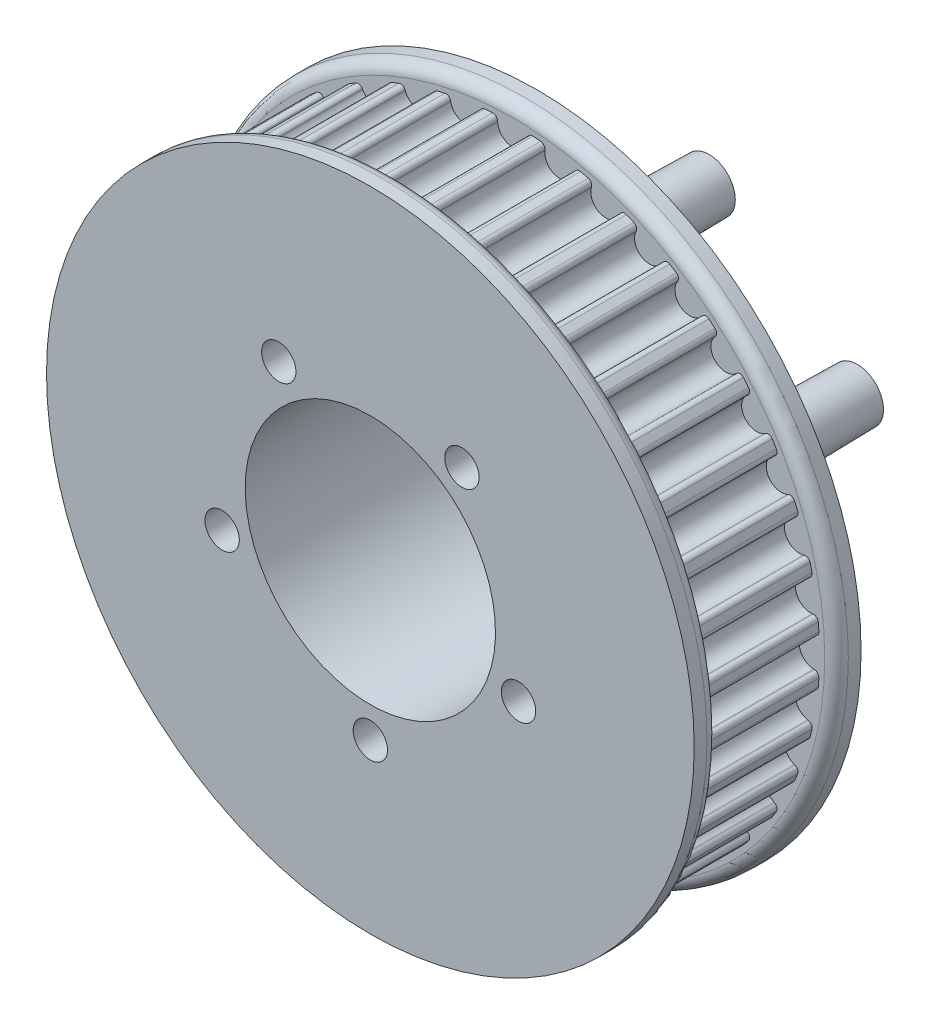
SolidWorks part; units mm, degrees
ref_plane "정면" through (0, 0, 0) normal (0, 0, 1) x (1, 0, 0)
ref_plane "윗면" through (0, 0, 0) normal (0, 1, 0) x (1, 0, 0)
ref_plane "우측면" through (0, 0, 0) normal (1, 0, 0) x (0, 0, -1)
sketch "스케치3" plane through (0, 0, 0) normal (0, 0, 1) x (1, 0, 0)
  line L0 (0, 0) -> (0, 31.2595) construction
  line L1 (0, 0) -> (-4.9795, 31.4391) construction
  line L2 (0, 31.2595) -> (0, 32.9895) construction
  line L3 (-1.5331, 30.6478) -> (-1.5617, 31.2205)
  line L4 (1.5331, 30.6478) -> (1.5617, 31.2205)
  circle A0 centre (0, 0) radius 31.831 construction
  circle A1 centre (0, 0) radius 32.9895 construction
  circle A2 centre (0, 0) radius 31.2595
  circle A3 centre (0, 30.7245) radius 1.535
  dimension "D2" = 63.662
  dimension "D5" = 3.07
  dimension "D3" = 62.519
  dimension "D1" = 9
  dimension "D4" = 2.07
  dimension "D6" = 3.8
extrude "보스-돌출2" add sketch "스케치3" along normal blind 12 contours A2
extrude "컷-돌출2" cut sketch "스케치3<3>" against normal through all and the other way through all contours A3 A2 L3 | A2 A3 | A3 L4 A2 region at (0, 30.3451, 0) region at (-1.5216, 31.0799, 0) region at (1.5216, 31.0799, 0)
sketch "스케치3<3>" plane through (0, 0, 0) normal (0, 0, 1) x (1, 0, 0) same geometry as "스케치3"
fillet "필렛1" radius 0.48 2 edges at (1.5617, 31.2205, 6) (-1.5617, 31.2205, 6)
pattern_circular "원형 패턴1" count 40 over 360 about axis through (0, 0, 12) along (0, 0, -1) of "컷-돌출2", "필렛1"
sketch "스케치8" plane through (0, 0, 12) normal (0, 0, 1) x (1, 0, 0)
  circle A1 centre (0, 0) radius 32.9895 construction
  circle A2 centre (0, 0) radius 32.9895
extrude "보스-돌출3" add sketch "스케치8" along normal blind 2.5
sketch "스케치9" plane through (0, 0, 0) normal (0, 0, -1) x (-1, 0, 0)
  circle A1 centre (0, 0) radius 32.9895 construction
  circle A3 centre (0, 0) radius 32.9895
extrude "보스-돌출4" add sketch "스케치9" along normal blind 2.5
sketch "스케치7" plane through (0, 0, 0) normal (-1, 0, 0) x (0, 0, 1)
  line L0 (-14.6599, 0) -> (-14.6599, 11)
  line L1 (-14.6599, 0) -> (-1.0048, 0)
  line L3 (-2.5, 32.9895) -> (-2.5, -32.9895) construction
  line L5 (-7.2548, 22.06) -> (-7.2548, 0) construction
  line L6 (-1.0048, 0) -> (-1.0048, 34.5)
  line L7 (0.2952, 26.3473) -> (-4.9, 29.3467)
  line L9 (-7.2548, 22.06) -> (0.2952, 22.06)
  line L10 (-7.2548, 22.06) -> (-10.1591, 0) construction
  line L13 (0.2952, 26.3473) -> (0.2952, 22.06)
  arc A0 (-14.6599, 11) -> (-7.2548, 22.06) centre (-2.698, 11) cw
  arc A1 (-7.2548, 22.06) -> (-1.0048, 34.5) centre (13.7562, 19.2938) cw
  dimension "D1" = 11
  dimension "D2" = 2.4
  dimension "D3" = 6.25
  dimension "D4" = 34.5
  dimension "D5" = 22.06
  dimension "D6" = 7.5
  dimension "D7" = 30
  dimension "D8" = 13.6551
  dimension "D10" = 7.55
  dimension "D11" = 3.8952
revolve "회전2" add sketch "스케치7" angle 360 about L1 region at (0, 10.341, -7.4409) region at (0, 25.0336, -3.8864)
sketch "스케치10" plane through (0, 0, 0) normal (0, 0, 1) x (1, 0, 0)
  line L0 (0, 0) -> (0, 15.875) construction
  circle A0 centre (0, 15.875) radius 2.675
  circle A1 centre (9.3311, 12.8431) radius 2.675 construction
  circle A2 centre (15.098, 4.9056) radius 2.675
  circle A3 centre (15.098, -4.9056) radius 2.675 construction
  circle A4 centre (9.3311, -12.8431) radius 2.675
  circle A5 centre (0, -15.875) radius 2.675 construction
  circle A6 centre (-9.3311, -12.8431) radius 2.675
  circle A7 centre (-15.098, -4.9056) radius 2.675 construction
  circle A8 centre (-15.098, 4.9056) radius 2.675
  circle A9 centre (-9.3311, 12.8431) radius 2.675 construction
  point P25 (0, 0)
  dimension "D1" = 5.35
  dimension "D2" = 15.875
  dimension "D3" = 10
extrude "보스-돌출5" add sketch "스케치10" against normal blind 20
hole_wizard "M5x0.8 탭을 위한 탭 드릴2" positions "스케치14" profile "스케치15" hole size "M5x0.8" standard "Ansi Metric" end condition through all
sketch "스케치14" plane through (0, 0, 14.5) normal (0, 0, -1) x (-1, 0, 0)
  point P26 (-15.098, -4.9056)
  point P28 (0, -15.875)
  point P30 (15.098, -4.9056)
  point P32 (9.3311, 12.8431)
  point P34 (-9.3311, 12.8431)
sketch "스케치15" plane through (15.098, -4.9056, 14.5) normal (1, 0, 0) x (0, -1, 0)
  line L0 (0, 0) -> (0, 34.5)
  line L1 (0, 34.5) -> (1.75, 34.5)
  line L2 (1.75, 34.5) -> (1.75, 0)
  line L5 (1.75, 0) -> (0, 0)
  line L11 (0, -6.35) -> (0, 107.95) construction
  dimension "관통 구멍 지름" = 3.5
  dimension "관통 구멍 깊이" = 34.5
draft "구배1" type of draft neutral plane draft angle 1 faces to draft 5 face at (17.2692, 6.4682, -12.064) face at (11.6645, -11.5352, -13.3692) face at (-6.94, -11.6438, -14.3838) face at (-13.0972, 6.6812, -14.0724) face at (1.7472, 17.9006, -12.4082) neutral plane through (0, 15.875, -20) neutral plane normal (0, 0, -1) parameters "D1"=1
sketch "스케치4" plane through (0, 0, -14.6599) normal (0, 0, -1) x (-1, 0, 0)
  circle A1 centre (0, 0) radius 12.75
  dimension "D1" = 25.5
extrude "컷-돌출3" cut sketch "스케치4" against normal through all
fillet "필렛2" radius 1.2 2 edges at (32.9895, 0, 12) (-32.9895, 0, 0)
sketch "스케치16" plane through (0, 0, -2.5) normal (0, 0, 1) x (1, 0, 0)
  circle A0 centre (0, 0) radius 22.5
  dimension "D1" = 45
extrude "컷-돌출4" [suppressed] cut sketch "스케치16" along normal through all from offset 10
sketch "스케치17" plane through (0, 0, 0) normal (1, 0, 0) x (0, 0, -1)
  line L0 (0, 0) -> (-50000, 0) construction
  line L2 (2.5, 32.9895) -> (2.5, 20)
  line L3 (2.5, -27.9611) -> (2.5, 27.9611) construction
  line L4 (2.5, 20) -> (8.2548, 20)
  line L5 (8.2548, 20) -> (8.2548, 0)
  line L7 (7.2548, 22.06) -> (7.2548, -22.06) construction
  dimension "D1" = 1
  dimension "D2" = 40
surface "곡면-회전1" [suppressed] sketch "스케치17" parameters "D1"=360
split "분할1" [suppressed] bodies to split 107
sketch "스케치18" plane through (0, 0, 14.5) normal (0, 0, 1) x (1, 0, 0)
  circle A0 centre (-15.098, -4.9056) radius 2.5
  dimension "D1" = 5
equation "\"n\"= 40'number of teeth"
equation "\"D2@스케치3\"=5*\"n\"/(PI)"
equation "\"D1@스케치3\"=360/\"n\""
equation "\"D1@원형 패턴1\"=\"n\""
equation "\"D3@스케치3\"=\"D2@스케치3\"-2*0.225*2.54"
